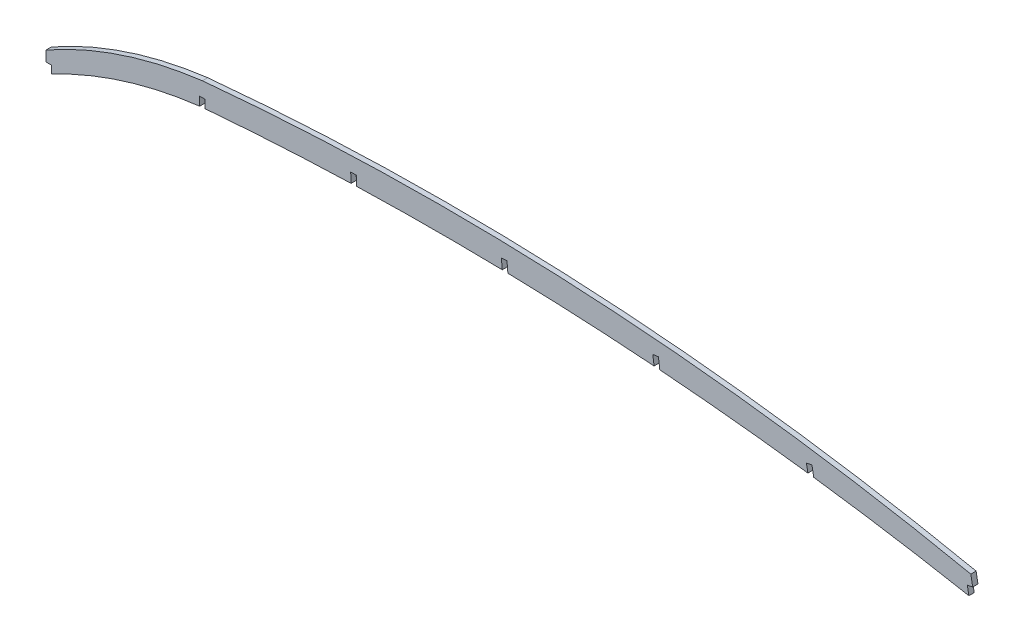
SolidWorks part; units mm, degrees
material "Plywood"
ref_plane "Front Plane" through (0, 0, 0) normal (0, 0, 1) x (1, 0, 0)
ref_plane "Top Plane" through (0, 0, 0) normal (0, 1, 0) x (1, 0, 0)
ref_plane "Right Plane" through (0, 0, 0) normal (1, 0, 0) x (0, 0, -1)
sketch "Sketch1" plane through (0, 0, 0) normal (0, 0, 1) x (1, 0, 0)
  line L2 (0, 0) -> (0, 169.3685) construction
  line L4 (93.98, 106.68) -> (556.5761, 106.68) construction
  line L9 (0, 106.68) -> (93.98, 106.68) construction
  line L14 (555.6382, 111.8229) -> (555.6382, 106.68) construction
  line L17 (555.6382, 111.8229) -> (557.917, 99.3265)
  line L19 (0, 106.68) -> (0, 93.98)
  line L20 (93.98, 137.668) -> (93.98, 123.7947) construction
  arc A6 (0, 106.68) -> (93.98, 137.668) centre (125.0054, -114.43) cw
  arc A8 (93.98, 137.668) -> (555.6382, 111.8229) centre (239.5165, -1398.7972) cw
  arc A9 (0, 93.98) -> (93.98, 123.7947) centre (122.3372, -128.6174) cw
  arc A25 (93.98, 123.7947) -> (557.917, 99.3265) centre (236.8486, -1577.8511) cw
  dimension "D4" = 254
  dimension "D2" = 93.98
  dimension "D8" = 1543.3426
  dimension "D9" = 100.334
  dimension "D3" = 30.988
  dimension "D12" = 254
  dimension "D14" = 1707.6328
  dimension "D1" = 106.68
  dimension "D5" = 462.5961
  dimension "D6" = 0.9378
  dimension "D7" = 5.1429
  dimension "D10" = 12.7025
  dimension "D11" = 12.7
  dimension "D13" = 13.8733
extrude "Boss-Extrude1" add sketch "Sketch1" against normal blind 3.175 contours A9 A25 L17 A8 A6 L19 region at (551.2665, 104.5698, 0)
sketch "Sketch2" plane through (0, 0, 0) normal (0, 0, 1) x (1, 0, 0)
  line L0 (0, 0) -> (0, 93.98) construction
  line L1 (0, 0) -> (93.98, 0) construction
  line L2 (93.98, 0) -> (93.98, 128.7725) construction
  line L3 (93.98, 0) -> (190.373, 0) construction
  line L4 (0, 93.98) -> (3.3528, 93.98)
  line L5 (0, 93.98) -> (0, 100.457)
  line L6 (0, 100.457) -> (3.3528, 100.457)
  line L7 (3.3528, 93.98) -> (3.3528, 100.457)
  line L8 (92.2909, 128.8487) -> (95.6691, 128.8487)
  line L9 (92.2909, 128.8487) -> (92.2909, 116.1487)
  line L10 (92.2909, 116.1487) -> (95.6691, 116.1487)
  line L11 (95.6691, 128.8487) -> (95.6691, 116.1487)
  line L12 (190.373, 0) -> (184.7454, 134.6815) construction
  line L13 (383.6414, 0) -> (367.0519, 124.8106) construction
  line L14 (367.0519, 124.8106) -> (366.2623, 130.7507) construction
  line L15 (183.0546, 134.6871) -> (186.4298, 134.8282)
  line L16 (183.0546, 134.6871) -> (183.5848, 121.9982)
  line L17 (186.4298, 134.8282) -> (186.96, 122.1393)
  line L18 (183.5848, 121.9982) -> (186.96, 122.1393)
  line L19 (480.4996, 0) -> (458.5303, 120.4774) construction
  line L20 (364.5779, 130.6037) -> (367.9267, 131.0488)
  line L21 (184.7454, 134.6815) -> (182.7802, 134.5994) construction
  line L23 (276.8619, 135.4735) -> (273.6986, 135.2013)
  line L24 (274.2432, 128.8746) -> (273.6986, 135.2013)
  line L26 (277.4065, 129.1469) -> (274.2432, 128.8746)
  line L27 (298.5367, -116.3253) -> (295.918, -122.9242)
  line L28 (276.8619, 135.4735) -> (277.41, 129.1062)
  line L29 (299.0813, -122.6519) -> (298.5367, -116.3253)
  line L38 (190.373, 0) -> (625.367, 0) construction
  line L39 (275.2802, 135.3374) -> (286.9301, 0) construction
  line L40 (364.5779, 130.6037) -> (365.8911, 120.7239)
  line L41 (273.5908, 135.2685) -> (276.9566, 135.5582)
  line L42 (273.5908, 135.2685) -> (274.68, 122.6152)
  line L43 (276.9566, 135.5582) -> (278.0458, 122.905)
  line L44 (274.68, 122.6152) -> (278.0458, 122.905)
  line L45 (367.9267, 131.0488) -> (369.2399, 121.169)
  line L46 (365.8911, 120.7239) -> (369.2399, 121.169)
  line L49 (295.3734, -116.5976) -> (298.5367, -116.3253)
  line L50 (456.855, 120.2494) -> (460.1784, 120.8554)
  line L51 (277.4065, 129.1469) -> (274.2432, 128.8746)
  line L52 (274.2432, 128.8746) -> (273.6986, 135.2013)
  line L53 (456.855, 120.2494) -> (458.4703, 111.3911)
  line L54 (460.1784, 120.8554) -> (461.7937, 111.9971)
  line L55 (458.4703, 111.3911) -> (461.7937, 111.9971)
  line L56 (295.918, -122.9242) -> (295.3734, -116.5976)
  line L59 (574.4157, 0) -> (555.2161, 105.2887) construction
  line L60 (553.5407, 105.0607) -> (556.8641, 105.6667)
  line L61 (553.5407, 105.0607) -> (555.334, 95.2267)
  line L62 (556.8641, 105.6667) -> (558.6574, 95.8327)
  line L63 (555.334, 95.2267) -> (558.6574, 95.8327)
  point P20 (184.7422, 134.7577)
  point P31 (275.2737, 135.4133)
  point P36 (93.98, 128.8487)
  point P37 (366.2523, 130.8263)
  point P42 (458.5167, 120.5524)
  point P44 (555.2024, 105.3637)
  arc M58 (0, 93.98) -> (93.98, 123.7947) centre (122.3372, -128.6174) cw
  arc M59 (93.98, 123.7947) -> (557.917, 99.3265) centre (236.8486, -1577.8511) cw
  line M60 (557.917, 99.3265) -> (555.6382, 111.8229)
  line M63 (0, 106.68) -> (0, 93.98)
  dimension "D1" = 93.98
  dimension "D2" = 6.477
  dimension "D3" = 3.3528
  dimension "D4" = 93.98
  dimension "D5" = 128.7725
  dimension "D6" = 3.3782
  dimension "D7" = 12.7
  dimension "D8" = 96.393
  dimension "D9" = 87.607
  dimension "D10" = 134.7991
  dimension "D11" = 0.0762
  dimension "D12" = 3.3782
  dimension "D13" = 85.08
  dimension "D14" = 96.5571
  dimension "D15" = 135.8379
  dimension "D16" = 0.0762
  dimension "D17" = 3.3782
  dimension "D18" = 12.7
  dimension "D19" = 12.7
  dimension "D20" = 0.0762
  dimension "D21" = 82.429
  dimension "D22" = 96.7113
  dimension "D23" = 125.9083
  dimension "D24" = 5.9924
  dimension "D25" = 0.0762
  dimension "D26" = 3.3782
  dimension "D27" = 79.666
  dimension "D28" = 96.8583
  dimension "D29" = 122.4641
  dimension "D30" = 3.3782
  dimension "D31" = 0.0762
  dimension "D32" = 79.666
  dimension "D33" = 93.9161
  dimension "D34" = 107.025
  dimension "D35" = 0.0762
  dimension "D36" = 3.3782
extrude "Cut-Extrude1" cut sketch "Sketch2" against normal through all contours L7 L6 M58 M63 | L11 L8 L9 M58 M59 | L17 L15 L16 M59 | L43 L41 L42 M59 | L45 L20 L40 M59 | L54 L50 L53 M59 | L60 L61 M59 M60 region at (555.7328, 102.5045, 0) region at (459.0612, 117.8798, 0) region at (366.6854, 127.8192, 0) region at (273.918, 132.3282, 0) region at (184.8645, 131.8757, 0) region at (93.9614, 126.3142, 0) region at (1.5856, 97.6492, 0) body kept at (556.7642, 105.6485, 0)
equation "\"slotwidth\"=0.167708"
